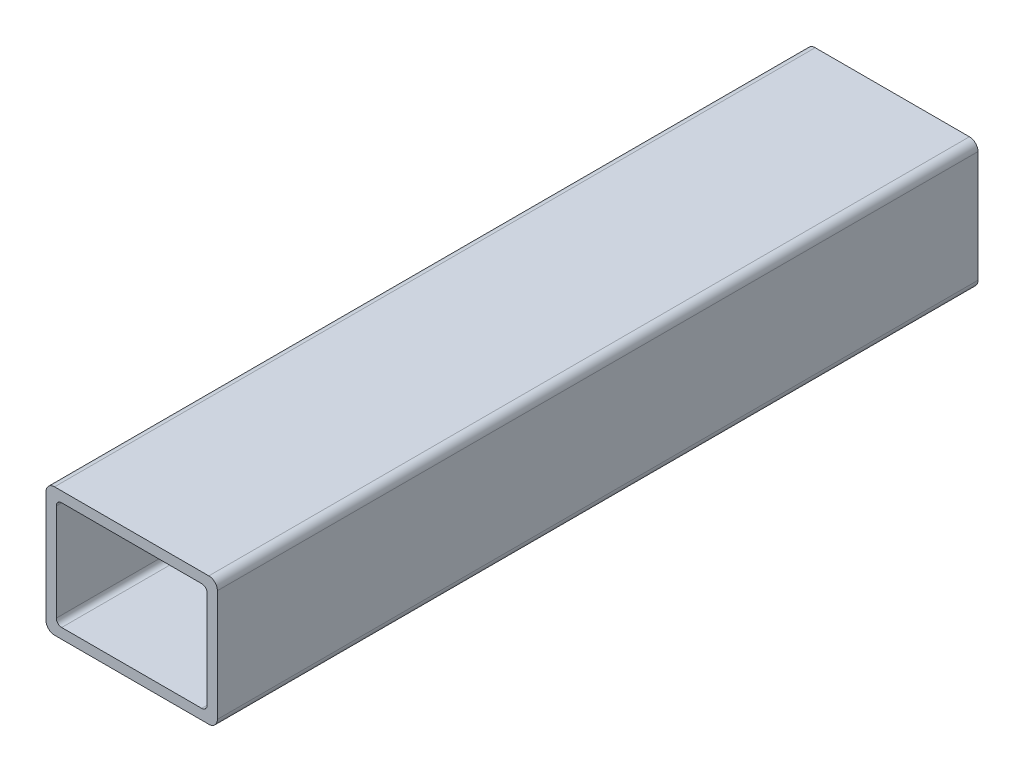
SolidWorks part; units mm, degrees
ref_plane "Front" through (0, 0, 0) normal (0, 0, 1) x (1, 0, 0)
ref_plane "Top" through (0, 0, 0) normal (0, 1, 0) x (1, 0, 0)
ref_plane "Right" through (0, 0, 0) normal (1, 0, 0) x (0, 0, -1)
sketch "Sketch1" plane through (0, 0, 0) normal (0, 0, 1) x (1, 0, 0)
  line L0 (-22.352, 0) -> (-25.4, 0) construction
  line L1 (22.86, -19.05) -> (-22.86, -19.05)
  line L2 (25.4, -16.51) -> (25.4, 16.51)
  line L3 (22.86, 19.05) -> (-22.86, 19.05)
  line L4 (-25.4, -16.51) -> (-25.4, 16.51)
  line L5 (25.4, -19.05) -> (-25.4, 19.05) construction
  line L6 (25.4, 19.05) -> (-25.4, -19.05) construction
  line L7 (20.7518, 16.002) -> (-20.7518, 16.002)
  line L8 (22.352, 14.4018) -> (22.352, -14.4018)
  line L9 (20.7518, -16.002) -> (-20.7518, -16.002)
  line L10 (-22.352, 14.4018) -> (-22.352, -14.4018)
  line L11 (22.352, 16.002) -> (-22.352, -16.002) construction
  line L12 (22.352, -16.002) -> (-22.352, 16.002) construction
  line L13 (0, -16.002) -> (0, -19.05) construction
  line L14 (22.352, -14.4018) -> (22.352, -19.05) construction
  line L16 (22.352, -19.05) -> (25.4, -19.05) construction
  arc A0 (-20.7518, -16.002) -> (-22.352, -14.4018) centre (-20.7518, -14.4018) cw
  arc A1 (22.352, -14.4018) -> (20.7518, -16.002) centre (20.7518, -14.4018) cw
  arc A2 (20.7518, 16.002) -> (22.352, 14.4018) centre (20.7518, 14.4018) cw
  arc A3 (-20.7518, 16.002) -> (-22.352, 14.4018) centre (-20.7518, 14.4018) ccw
  arc A4 (22.86, -19.05) -> (25.4, -16.51) centre (22.86, -16.51) ccw
  arc A5 (25.4, 16.51) -> (22.86, 19.05) centre (22.86, 16.51) ccw
  arc A6 (-22.86, 19.05) -> (-25.4, 16.51) centre (-22.86, 16.51) ccw
  arc A7 (-22.86, -19.05) -> (-25.4, -16.51) centre (-22.86, -16.51) cw
  point P0 (0, 0)
  point P6 (0, 0)
  dimension "D2" = 1.6002
  dimension "D3" = 2.54
sketch "Sketch2" plane through (0, 0, 0) normal (1, 0, 0) x (0, 0, -1)
  line L0 (-152.4, 0) -> (152.4, 0) construction
  dimension "Length" = 304.8
ref_plane "Plane1" through (25.4, 0, 0) normal (1, 0, 0) x (0, 0, -1)
sketch "Sketch5" plane through (25.4, 0, 0) normal (1, 0, 0) x (0, 0, -1)
  line L0 (-152.4, 19.05) -> (-152.4, -19.05) construction
  line L1 (152.4, 19.05) -> (152.4, -19.05) construction
sketch "Sketch4" plane through (0, 0, 0) normal (0, 0, 1) x (1, 0, 0)
  line L0 (25.4, -16.51) -> (25.4, 16.51) construction
  line L1 (22.86, 19.05) -> (-22.86, 19.05) construction
  line L2 (-25.4, -16.51) -> (-25.4, 16.51) construction
  line L3 (22.86, -19.05) -> (-22.86, -19.05) construction
  line L4 (22.352, 14.4018) -> (22.352, -14.4018) construction
  line L5 (20.7518, -16.002) -> (-20.7518, -16.002) construction
  line L6 (-22.352, 14.4018) -> (-22.352, -14.4018) construction
  line L7 (20.7518, 16.002) -> (-20.7518, 16.002) construction
  line L8 (25.4, -16.51) -> (25.4, 16.51)
  line L9 (22.86, 19.05) -> (-22.86, 19.05)
  line L10 (-25.4, -16.51) -> (-25.4, 16.51)
  line L11 (22.86, -19.05) -> (-22.86, -19.05)
  line L12 (22.352, 14.4018) -> (22.352, -14.4018)
  line L13 (20.7518, -16.002) -> (-20.7518, -16.002)
  line L14 (-22.352, 14.4018) -> (-22.352, -14.4018)
  line L15 (20.7518, 16.002) -> (-20.7518, 16.002)
  arc A0 (25.4, 16.51) -> (22.86, 19.05) centre (22.86, 16.51) ccw construction
  arc A1 (-22.86, 19.05) -> (-25.4, 16.51) centre (-22.86, 16.51) ccw construction
  arc A2 (-25.4, -16.51) -> (-22.86, -19.05) centre (-22.86, -16.51) ccw construction
  arc A3 (22.86, -19.05) -> (25.4, -16.51) centre (22.86, -16.51) ccw construction
  arc A4 (20.7518, -16.002) -> (22.352, -14.4018) centre (20.7518, -14.4018) ccw construction
  arc A5 (-22.352, -14.4018) -> (-20.7518, -16.002) centre (-20.7518, -14.4018) ccw construction
  arc A6 (-20.7518, 16.002) -> (-22.352, 14.4018) centre (-20.7518, 14.4018) ccw construction
  arc A7 (22.352, 14.4018) -> (20.7518, 16.002) centre (20.7518, 14.4018) ccw construction
  arc A8 (25.4, 16.51) -> (22.86, 19.05) centre (22.86, 16.51) ccw
  arc A9 (-22.86, 19.05) -> (-25.4, 16.51) centre (-22.86, 16.51) ccw
  arc A10 (-25.4, -16.51) -> (-22.86, -19.05) centre (-22.86, -16.51) ccw
  arc A11 (22.86, -19.05) -> (25.4, -16.51) centre (22.86, -16.51) ccw
  arc A12 (20.7518, -16.002) -> (22.352, -14.4018) centre (20.7518, -14.4018) ccw
  arc A13 (-22.352, -14.4018) -> (-20.7518, -16.002) centre (-20.7518, -14.4018) ccw
  arc A14 (-20.7518, 16.002) -> (-22.352, 14.4018) centre (-20.7518, 14.4018) ccw
  arc A15 (22.352, 14.4018) -> (20.7518, 16.002) centre (20.7518, 14.4018) ccw
extrude "Boss-Extrude1" add sketch "Sketch4" along normal blind 225.425
sketch "Sketch6" plane through (0, 19.05, 0) normal (0, 1, 0) x (1, 0, 0)
  line L0 (0, -225.425) -> (0, -182.5625) construction
  line L2 (-22.86, -182.5625) -> (22.86, -182.5625) construction
  line L3 (-22.86, 0) -> (-22.86, -225.425) construction
  line L4 (22.86, 0) -> (22.86, -225.425) construction
  line L5 (-22.86, -42.8625) -> (22.86, -42.8625) construction
  line L6 (22.86, -225.425) -> (-22.86, -225.425) construction
  line L7 (0, -182.5625) -> (0, -42.8625) construction
  line L8 (0, -42.8625) -> (0, 0) construction
  line L9 (22.86, 0) -> (-22.86, 0) construction
  dimension "D1" = 139.7
equation "\"D3@Sketch1\"=\"Outside Width@Sketch1\"*.05"
equation "\"D2@Sketch1\"=\"D1@Sketch1\"*.05"
